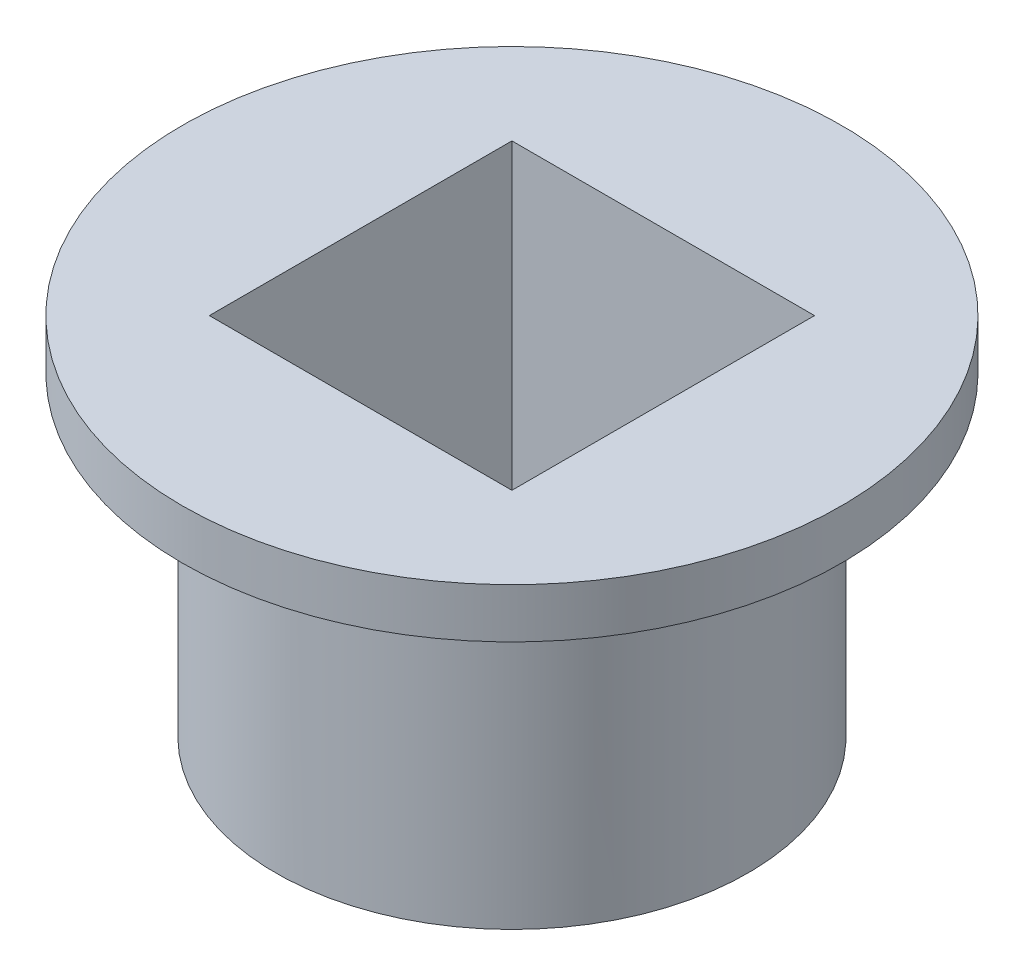
SolidWorks part; units mm, degrees
ref_plane "Front Plane" through (0, 0, 0) normal (0, 0, 1) x (1, 0, 0)
ref_plane "Top Plane" through (0, 0, 0) normal (0, 1, 0) x (1, 0, 0)
ref_plane "Right Plane" through (0, 0, 0) normal (1, 0, 0) x (0, 0, -1)
sketch "Sketch1" plane through (0, 0, 0) normal (0, 1, 0) x (1, 0, 0)
  line L0 (-6.1, -6.1) -> (6.1, -6.1)
  line L1 (-6.1, -6.1) -> (-6.1, 6.1)
  line L2 (6.1, -6.1) -> (6.1, 6.1)
  line L3 (-6.1, 6.1) -> (6.1, 6.1)
  line L4 (-6.1, -6.1) -> (6.1, 6.1) construction
  line L5 (6.1, -6.1) -> (-6.1, 6.1) construction
  circle A0 centre (0, 0) radius 9.525
  point P1 (0, 0)
  dimension "D3" = 19.05
  dimension "D1" = 12.2
  dimension "D2" = 12.2
extrude "Boss-Extrude1" add sketch "Sketch1" along normal blind 12.7
sketch "Sketch2" plane through (0, 12.7, 0) normal (0, 1, 0) x (1, 0, 0)
  circle A1 centre (0, 0) radius 9.525 construction
  circle A3 centre (0, 0) radius 13.2875
  circle A4 centre (0, 0) radius 9.525
  dimension "D1" = 26.575
extrude "Boss-Extrude3" add sketch "Sketch2" against normal blind 2
sketch "Sketch3" plane through (0, 0, 0) normal (0, -1, 0) x (1, 0, 0)
  circle A0 centre (0, 0) radius 9.525 construction
  circle A1 centre (0, 0) radius 9.525
  circle A2 centre (0, 0) radius 4.6
  dimension "D1" = 9.2
extrude "Boss-Extrude4" add sketch "Sketch3" along normal blind 2
